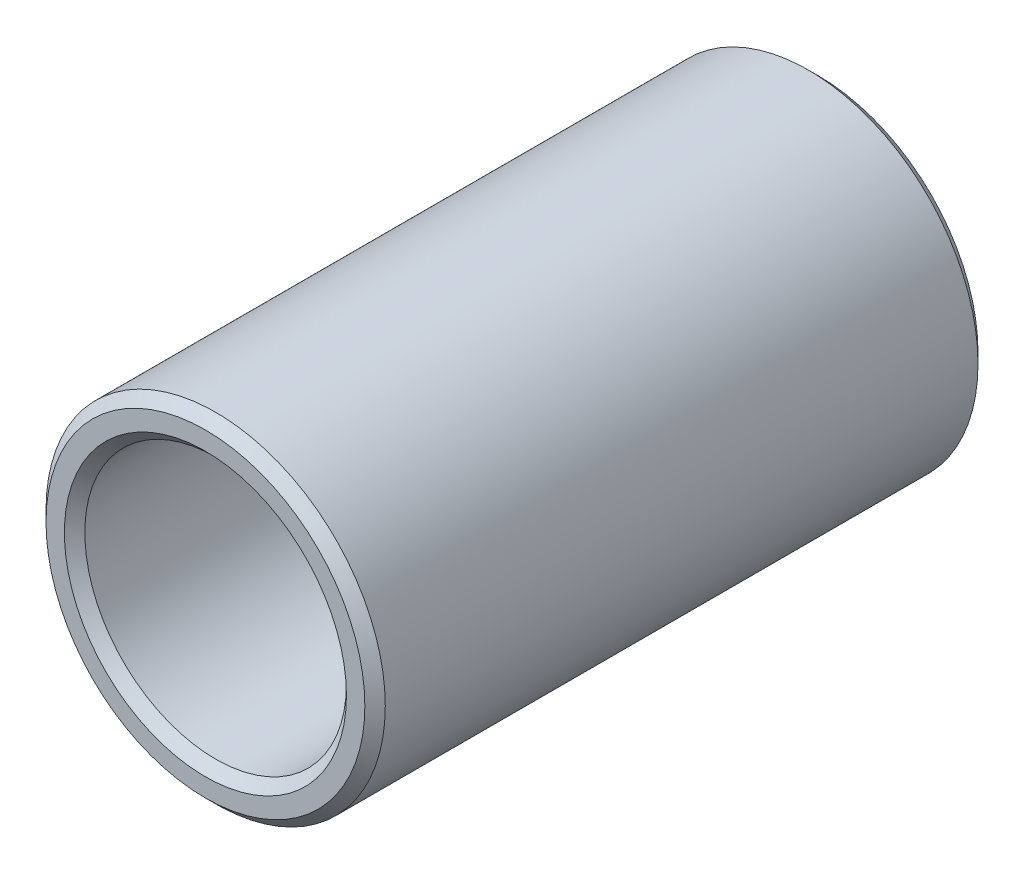
SolidWorks part; units mm, degrees
material "ABS"
ref_plane "Front Plane" through (0, 0, 0) normal (0, 0, 1) x (1, 0, 0)
ref_plane "Top Plane" through (0, 0, 0) normal (0, 1, 0) x (1, 0, 0)
ref_plane "Right Plane" through (0, 0, 0) normal (1, 0, 0) x (0, 0, -1)
sketch "Sketch1" plane through (0, 0, 0) normal (0, 0, 1) x (1, 0, 0)
  circle A0 centre (0, 0) radius 4.15
  circle A1 centre (0, 0) radius 3.2
  dimension "D1" = 6.4
  dimension "D2" = 8.3
extrude "Boss-Extrude1" add sketch "Sketch1" along normal blind 15
chamfer "Chamfer1" distance 0.25 angle 45 4 edges at (3.2, 0, 15) (4.15, 0, 15) (3.2, 0, 0) (4.15, 0, 0)
